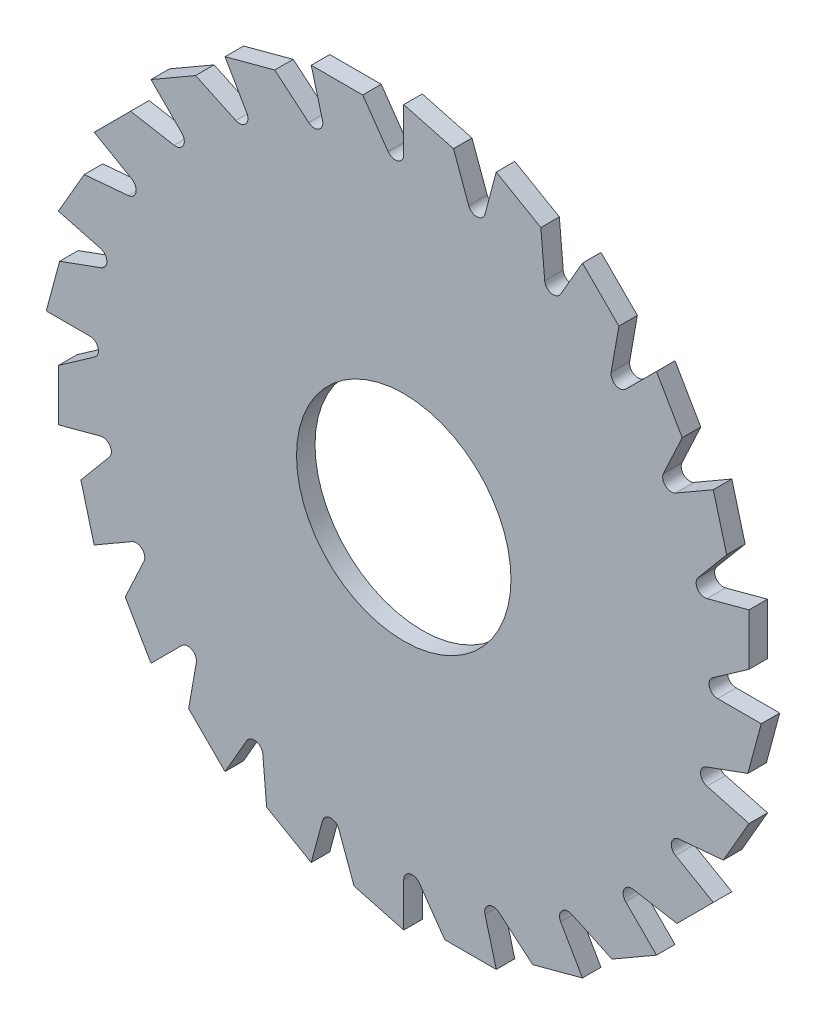
SolidWorks part; units mm, degrees
ref_plane "Front Plane" through (0, 0, 0) normal (0, 0, 1) x (1, 0, 0)
ref_plane "Top Plane" through (0, 0, 0) normal (0, 1, 0) x (1, 0, 0)
ref_plane "Right Plane" through (0, 0, 0) normal (1, 0, 0) x (0, 0, -1)
sketch "Sketch1" plane through (0, 0, 0) normal (0, 0, 1) x (1, 0, 0)
  line L0 (0, 31.75) -> (4.4162, 30.5667)
  line L1 (4.4162, 30.5667) -> (5.7634, 26.8652)
  line L2 (7.2155, 26.9286) -> (8.2175, 30.6681)
  line L3 (0, 31.75) -> (0, 0) construction
  line L4 (0, 0) -> (8.2175, 30.6681) construction
  line L5 (0, 31.75) -> (12.0811, 31.75) construction
  line L6 (6.3024, 26.3847) -> (0, 0) construction
  line L7 (6.3024, 26.3847) -> (4.0698, 26.918) construction
  line L8 (13.9393, 24.1436) -> (15.875, 27.4963)
  line L9 (12.177, 28.3821) -> (12.5203, 24.4581)
  line L10 (8.2175, 30.6681) -> (12.177, 28.3821)
  line L11 (19.7131, 19.7131) -> (22.4506, 22.4506)
  line L12 (19.1079, 24.2634) -> (18.4239, 20.3843)
  line L13 (15.875, 27.4963) -> (19.1079, 24.2634)
  line L14 (24.1436, 13.9393) -> (27.4963, 15.875)
  line L15 (24.7366, 18.4912) -> (23.072, 14.9212)
  line L16 (22.4506, 22.4506) -> (24.7366, 18.4912)
  line L17 (26.9286, 7.2155) -> (30.6681, 8.2175)
  line L18 (28.6796, 11.4588) -> (26.1477, 8.4413)
  line L19 (27.4963, 15.875) -> (28.6796, 11.4588)
  line L20 (27.8786, 0) -> (31.75, 0)
  line L21 (30.6681, 3.6455) -> (27.4415, 1.3862)
  line L22 (30.6681, 8.2175) -> (30.6681, 3.6455)
  line L23 (26.9286, -7.2155) -> (30.6681, -8.2175)
  line L24 (30.5667, -4.4162) -> (26.8652, -5.7634)
  line L25 (31.75, 0) -> (30.5667, -4.4162)
  line L26 (24.1436, -13.9393) -> (27.4963, -15.875)
  line L27 (28.3821, -12.177) -> (24.4581, -12.5203)
  line L28 (30.6681, -8.2175) -> (28.3821, -12.177)
  line L29 (19.7131, -19.7131) -> (22.4506, -22.4506)
  line L30 (24.2634, -19.1079) -> (20.3843, -18.4239)
  line L31 (27.4963, -15.875) -> (24.2634, -19.1079)
  line L32 (13.9393, -24.1436) -> (15.875, -27.4963)
  line L33 (18.4912, -24.7366) -> (14.9212, -23.072)
  line L34 (22.4506, -22.4506) -> (18.4912, -24.7366)
  line L35 (7.2155, -26.9286) -> (8.2175, -30.6681)
  line L36 (11.4588, -28.6796) -> (8.4413, -26.1477)
  line L37 (15.875, -27.4963) -> (11.4588, -28.6796)
  line L38 (0, -27.8786) -> (0, -31.75)
  line L39 (3.6455, -30.6681) -> (1.3862, -27.4415)
  line L40 (8.2175, -30.6681) -> (3.6455, -30.6681)
  line L41 (-7.2155, -26.9286) -> (-8.2175, -30.6681)
  line L42 (-4.4162, -30.5667) -> (-5.7634, -26.8652)
  line L43 (0, -31.75) -> (-4.4162, -30.5667)
  line L44 (-13.9393, -24.1436) -> (-15.875, -27.4963)
  line L45 (-12.177, -28.3821) -> (-12.5203, -24.4581)
  line L46 (-8.2175, -30.6681) -> (-12.177, -28.3821)
  line L47 (-19.7131, -19.7131) -> (-22.4506, -22.4506)
  line L48 (-19.1079, -24.2634) -> (-18.4239, -20.3843)
  line L49 (-15.875, -27.4963) -> (-19.1079, -24.2634)
  line L50 (-24.1436, -13.9393) -> (-27.4963, -15.875)
  line L51 (-24.7366, -18.4912) -> (-23.072, -14.9212)
  line L52 (-22.4506, -22.4506) -> (-24.7366, -18.4912)
  line L53 (-26.9286, -7.2155) -> (-30.6681, -8.2175)
  line L54 (-28.6796, -11.4588) -> (-26.1477, -8.4413)
  line L55 (-27.4963, -15.875) -> (-28.6796, -11.4588)
  line L56 (-27.8786, 0) -> (-31.75, 0)
  line L57 (-30.6681, -3.6455) -> (-27.4415, -1.3862)
  line L58 (-30.6681, -8.2175) -> (-30.6681, -3.6455)
  line L59 (-26.9286, 7.2155) -> (-30.6681, 8.2175)
  line L60 (-30.5667, 4.4162) -> (-26.8652, 5.7634)
  line L61 (-31.75, 0) -> (-30.5667, 4.4162)
  line L62 (-24.1436, 13.9393) -> (-27.4963, 15.875)
  line L63 (-28.3821, 12.177) -> (-24.4581, 12.5203)
  line L64 (-30.6681, 8.2175) -> (-28.3821, 12.177)
  line L65 (-19.7131, 19.7131) -> (-22.4506, 22.4506)
  line L66 (-24.2634, 19.1079) -> (-20.3843, 18.4239)
  line L67 (-27.4963, 15.875) -> (-24.2634, 19.1079)
  line L68 (-13.9393, 24.1436) -> (-15.875, 27.4963)
  line L69 (-18.4912, 24.7366) -> (-14.9212, 23.072)
  line L70 (-22.4506, 22.4506) -> (-18.4912, 24.7366)
  line L71 (-7.2155, 26.9286) -> (-8.2175, 30.6681)
  line L72 (-11.4588, 28.6796) -> (-8.4413, 26.1477)
  line L73 (-15.875, 27.4963) -> (-11.4588, 28.6796)
  line L74 (0, 27.8786) -> (0, 31.75)
  line L75 (-3.6455, 30.6681) -> (-1.3862, 27.4415)
  line L76 (-8.2175, 30.6681) -> (-3.6455, 30.6681)
  circle A0 centre (0, 0) radius 31.75 construction
  circle A1 centre (0, 0) radius 9.525
  circle A2 centre (0, 0) radius 27.127 construction
  arc A3 (5.7634, 26.8652) -> (7.2155, 26.9286) centre (6.4795, 27.1259) ccw
  arc A4 (12.5203, 24.4581) -> (13.9393, 24.1436) centre (13.2794, 24.5246) ccw
  arc A5 (18.4239, 20.3843) -> (19.7131, 19.7131) centre (19.1743, 20.2519) ccw
  arc A6 (23.072, 14.9212) -> (24.1436, 13.9393) centre (23.7626, 14.5992) ccw
  arc A7 (26.1477, 8.4413) -> (26.9286, 7.2155) centre (26.7314, 7.9515) ccw
  arc A8 (27.4415, 1.3862) -> (27.8786, 0) centre (27.8786, 0.762) ccw
  arc A9 (26.8652, -5.7634) -> (26.9286, -7.2155) centre (27.1259, -6.4795) ccw
  arc A10 (24.4581, -12.5203) -> (24.1436, -13.9393) centre (24.5246, -13.2794) ccw
  arc A11 (20.3843, -18.4239) -> (19.7131, -19.7131) centre (20.2519, -19.1743) ccw
  arc A12 (14.9212, -23.072) -> (13.9393, -24.1436) centre (14.5992, -23.7626) ccw
  arc A13 (8.4413, -26.1477) -> (7.2155, -26.9286) centre (7.9515, -26.7314) ccw
  arc A14 (1.3862, -27.4415) -> (0, -27.8786) centre (0.762, -27.8786) ccw
  arc A15 (-5.7634, -26.8652) -> (-7.2155, -26.9286) centre (-6.4795, -27.1259) ccw
  arc A16 (-12.5203, -24.4581) -> (-13.9393, -24.1436) centre (-13.2794, -24.5246) ccw
  arc A17 (-18.4239, -20.3843) -> (-19.7131, -19.7131) centre (-19.1743, -20.2519) ccw
  arc A18 (-23.072, -14.9212) -> (-24.1436, -13.9393) centre (-23.7626, -14.5992) ccw
  arc A19 (-26.1477, -8.4413) -> (-26.9286, -7.2155) centre (-26.7314, -7.9515) ccw
  arc A20 (-27.4415, -1.3862) -> (-27.8786, 0) centre (-27.8786, -0.762) ccw
  arc A21 (-26.8652, 5.7634) -> (-26.9286, 7.2155) centre (-27.1259, 6.4795) ccw
  arc A22 (-24.4581, 12.5203) -> (-24.1436, 13.9393) centre (-24.5246, 13.2794) ccw
  arc A23 (-20.3843, 18.4239) -> (-19.7131, 19.7131) centre (-20.2519, 19.1743) ccw
  arc A24 (-14.9212, 23.072) -> (-13.9393, 24.1436) centre (-14.5992, 23.7626) ccw
  arc A25 (-8.4413, 26.1477) -> (-7.2155, 26.9286) centre (-7.9515, 26.7314) ccw
  arc A26 (-1.3862, 27.4415) -> (0, 27.8786) centre (-0.762, 27.8786) ccw
  dimension "D1" = 63.5
  dimension "D2" = 19.05
  dimension "D3" = 125
  dimension "D7" = 0.762
  dimension "D4" = 15
  dimension "D5" = 15
  dimension "D6" = 4.572
  dimension "D8" = 24
extrude "Boss-Extrude1" add sketch "Sketch1" along normal blind 1.6444 contours A26 L75 L76 L71 A25 L72 L73 L68 A24 L69 L70 L65 A23 L66 L67 L62 A22 L63 L64 L59 A21 L60 L61 L56 A20 L57 L58 L53 A19 L54 L55 L50 A18 L51 L52 L47 A17 L48 L49 L44 A16 L45 L46 L41 A15 L42 L43 L38 A14 L39 L40 region at (1.9757, 30.2909, 0)
ref_plane "Plane1" through (0, 0, 0.8222) normal (0, 0, 1) x (1, 0, 0)
sketch "Sketch2" plane through (0, 0, 0) normal (0, 0, 1) x (1, 0, 0)
  line L0 (31.75, -31.75) -> (31.75, 31.75)
  line L1 (400.05, -31.75) -> (-31.75, -31.75)
  line L2 (400.05, -31.75) -> (400.05, 400.05)
  line L3 (400.05, 400.05) -> (-31.75, 400.05)
  line L4 (-31.75, -31.75) -> (-31.75, 400.05)
  line L5 (184.15, 400.05) -> (184.15, -31.75) construction
  line L6 (400.05, 184.15) -> (-31.75, 184.15) construction
  line L7 (-31.75, -31.75) -> (31.75, -31.75)
  line L8 (-31.75, -31.75) -> (-31.75, 31.75)
  line L9 (-31.75, 31.75) -> (31.75, 31.75)
  line L10 (31.75, -31.75) -> (31.75, 31.75)
  line L11 (0, 31.75) -> (0, -31.75) construction
  line L12 (-31.75, 0) -> (31.75, 0) construction
  line L13 (31.75, -31.75) -> (95.25, -31.75)
  line L14 (95.25, -31.75) -> (95.25, 31.75)
  line L15 (31.75, 31.75) -> (95.25, 31.75)
  line L16 (95.25, -31.75) -> (95.25, 31.75)
  line L17 (95.25, -31.75) -> (158.75, -31.75)
  line L18 (158.75, -31.75) -> (158.75, 31.75)
  line L19 (95.25, 31.75) -> (158.75, 31.75)
  line L20 (158.75, -31.75) -> (158.75, 31.75)
  line L21 (158.75, -31.75) -> (222.25, -31.75)
  line L22 (222.25, -31.75) -> (222.25, 31.75)
  line L23 (158.75, 31.75) -> (222.25, 31.75)
  line L24 (222.25, -31.75) -> (222.25, 31.75)
  line L25 (222.25, -31.75) -> (285.75, -31.75)
  line L26 (285.75, -31.75) -> (285.75, 31.75)
  line L27 (222.25, 31.75) -> (285.75, 31.75)
  line L28 (285.75, -31.75) -> (285.75, 31.75)
  line L29 (285.75, -31.75) -> (349.25, -31.75)
  line L30 (349.25, -31.75) -> (349.25, 31.75)
  line L31 (285.75, 31.75) -> (349.25, 31.75)
  line L32 (31.75, 31.75) -> (31.75, 95.25)
  line L33 (31.75, 31.75) -> (95.25, 31.75)
  line L34 (95.25, 31.75) -> (95.25, 95.25)
  line L35 (31.75, 95.25) -> (95.25, 95.25)
  line L36 (95.25, 31.75) -> (95.25, 95.25)
  line L37 (95.25, 31.75) -> (158.75, 31.75)
  line L38 (158.75, 31.75) -> (158.75, 95.25)
  line L39 (95.25, 95.25) -> (158.75, 95.25)
  line L40 (158.75, 31.75) -> (158.75, 95.25)
  line L41 (158.75, 31.75) -> (222.25, 31.75)
  line L42 (222.25, 31.75) -> (222.25, 95.25)
  line L43 (158.75, 95.25) -> (222.25, 95.25)
  line L44 (222.25, 31.75) -> (222.25, 95.25)
  line L45 (222.25, 31.75) -> (285.75, 31.75)
  line L46 (285.75, 31.75) -> (285.75, 95.25)
  line L47 (222.25, 95.25) -> (285.75, 95.25)
  line L48 (285.75, 31.75) -> (285.75, 95.25)
  line L49 (285.75, 31.75) -> (349.25, 31.75)
  line L50 (349.25, 31.75) -> (349.25, 95.25)
  line L51 (285.75, 95.25) -> (349.25, 95.25)
  line L52 (31.75, 95.25) -> (31.75, 158.75)
  line L53 (31.75, 95.25) -> (95.25, 95.25)
  line L54 (95.25, 95.25) -> (95.25, 158.75)
  line L55 (31.75, 158.75) -> (95.25, 158.75)
  line L56 (95.25, 95.25) -> (95.25, 158.75)
  line L57 (95.25, 95.25) -> (158.75, 95.25)
  line L58 (158.75, 95.25) -> (158.75, 158.75)
  line L59 (95.25, 158.75) -> (158.75, 158.75)
  line L60 (158.75, 95.25) -> (158.75, 158.75)
  line L61 (158.75, 95.25) -> (222.25, 95.25)
  line L62 (222.25, 95.25) -> (222.25, 158.75)
  line L63 (158.75, 158.75) -> (222.25, 158.75)
  line L64 (222.25, 95.25) -> (222.25, 158.75)
  line L65 (222.25, 95.25) -> (285.75, 95.25)
  line L66 (285.75, 95.25) -> (285.75, 158.75)
  line L67 (222.25, 158.75) -> (285.75, 158.75)
  line L68 (285.75, 95.25) -> (285.75, 158.75)
  line L69 (285.75, 95.25) -> (349.25, 95.25)
  line L70 (349.25, 95.25) -> (349.25, 158.75)
  line L71 (285.75, 158.75) -> (349.25, 158.75)
  line L72 (31.75, 158.75) -> (31.75, 222.25)
  line L73 (31.75, 158.75) -> (95.25, 158.75)
  line L74 (95.25, 158.75) -> (95.25, 222.25)
  line L75 (31.75, 222.25) -> (95.25, 222.25)
  line L76 (95.25, 158.75) -> (95.25, 222.25)
  line L77 (95.25, 158.75) -> (158.75, 158.75)
  line L78 (158.75, 158.75) -> (158.75, 222.25)
  line L79 (95.25, 222.25) -> (158.75, 222.25)
  line L80 (158.75, 158.75) -> (158.75, 222.25)
  line L81 (158.75, 158.75) -> (222.25, 158.75)
  line L82 (222.25, 158.75) -> (222.25, 222.25)
  line L83 (158.75, 222.25) -> (222.25, 222.25)
  line L84 (222.25, 158.75) -> (222.25, 222.25)
  line L85 (222.25, 158.75) -> (285.75, 158.75)
  line L86 (285.75, 158.75) -> (285.75, 222.25)
  line L87 (222.25, 222.25) -> (285.75, 222.25)
  line L88 (285.75, 158.75) -> (285.75, 222.25)
  line L89 (285.75, 158.75) -> (349.25, 158.75)
  line L90 (349.25, 158.75) -> (349.25, 222.25)
  line L91 (285.75, 222.25) -> (349.25, 222.25)
  line L92 (31.75, 222.25) -> (31.75, 285.75)
  line L93 (31.75, 222.25) -> (95.25, 222.25)
  line L94 (95.25, 222.25) -> (95.25, 285.75)
  line L95 (31.75, 285.75) -> (95.25, 285.75)
  line L96 (95.25, 222.25) -> (95.25, 285.75)
  line L97 (95.25, 222.25) -> (158.75, 222.25)
  line L98 (158.75, 222.25) -> (158.75, 285.75)
  line L99 (95.25, 285.75) -> (158.75, 285.75)
  line L100 (158.75, 222.25) -> (158.75, 285.75)
  line L101 (158.75, 222.25) -> (222.25, 222.25)
  line L102 (222.25, 222.25) -> (222.25, 285.75)
  line L103 (158.75, 285.75) -> (222.25, 285.75)
  line L104 (222.25, 222.25) -> (222.25, 285.75)
  line L105 (222.25, 222.25) -> (285.75, 222.25)
  line L106 (285.75, 222.25) -> (285.75, 285.75)
  line L107 (222.25, 285.75) -> (285.75, 285.75)
  line L108 (285.75, 222.25) -> (285.75, 285.75)
  line L109 (285.75, 222.25) -> (349.25, 222.25)
  line L110 (349.25, 222.25) -> (349.25, 285.75)
  line L111 (285.75, 285.75) -> (349.25, 285.75)
  line L112 (31.75, 285.75) -> (31.75, 349.25)
  line L113 (31.75, 285.75) -> (95.25, 285.75)
  line L114 (95.25, 285.75) -> (95.25, 349.25)
  line L115 (31.75, 349.25) -> (95.25, 349.25)
  line L116 (95.25, 285.75) -> (95.25, 349.25)
  line L117 (95.25, 285.75) -> (158.75, 285.75)
  line L118 (158.75, 285.75) -> (158.75, 349.25)
  line L119 (95.25, 349.25) -> (158.75, 349.25)
  line L120 (158.75, 285.75) -> (158.75, 349.25)
  line L121 (158.75, 285.75) -> (222.25, 285.75)
  line L122 (222.25, 285.75) -> (222.25, 349.25)
  line L123 (158.75, 349.25) -> (222.25, 349.25)
  line L124 (222.25, 285.75) -> (222.25, 349.25)
  line L125 (222.25, 285.75) -> (285.75, 285.75)
  line L126 (285.75, 285.75) -> (285.75, 349.25)
  line L127 (222.25, 349.25) -> (285.75, 349.25)
  line L128 (285.75, 285.75) -> (285.75, 349.25)
  line L129 (285.75, 285.75) -> (349.25, 285.75)
  line L130 (349.25, 285.75) -> (349.25, 349.25)
  line L131 (285.75, 349.25) -> (349.25, 349.25)
  line L132 (-31.75, 31.75) -> (-31.75, 95.25)
  line L133 (-31.75, 31.75) -> (31.75, 31.75)
  line L134 (31.75, 31.75) -> (31.75, 95.25)
  line L135 (-31.75, 95.25) -> (31.75, 95.25)
  line L136 (-31.75, 95.25) -> (-31.75, 158.75)
  line L137 (-31.75, 95.25) -> (31.75, 95.25)
  line L138 (31.75, 95.25) -> (31.75, 158.75)
  line L139 (-31.75, 158.75) -> (31.75, 158.75)
  line L140 (-31.75, 158.75) -> (-31.75, 222.25)
  line L141 (-31.75, 158.75) -> (31.75, 158.75)
  line L142 (31.75, 158.75) -> (31.75, 222.25)
  line L143 (-31.75, 222.25) -> (31.75, 222.25)
  line L144 (-31.75, 222.25) -> (-31.75, 285.75)
  line L145 (-31.75, 222.25) -> (31.75, 222.25)
  line L146 (31.75, 222.25) -> (31.75, 285.75)
  line L147 (-31.75, 285.75) -> (31.75, 285.75)
  line L148 (-31.75, 285.75) -> (-31.75, 349.25)
  line L149 (-31.75, 285.75) -> (31.75, 285.75)
  line L150 (31.75, 285.75) -> (31.75, 349.25)
  line L151 (-31.75, 349.25) -> (31.75, 349.25)
  line L152 (-31.75, -31.75) -> (31.75, -31.75) construction
  line L153 (-31.75, -31.75) -> (-31.75, 31.75) construction
  line L155 (-31.75, 400.05) -> (57.15, 400.05)
  line L156 (-31.75, 400.05) -> (-31.75, 349.25)
  line L157 (-31.75, 349.25) -> (57.15, 349.25)
  line L158 (57.15, 400.05) -> (57.15, 349.25)
  line L159 (57.15, 400.05) -> (146.05, 400.05)
  line L160 (57.15, 400.05) -> (57.15, 349.25)
  line L161 (57.15, 349.25) -> (146.05, 349.25)
  line L162 (146.05, 400.05) -> (146.05, 349.25)
  line L163 (146.05, 400.05) -> (234.95, 400.05)
  line L164 (146.05, 400.05) -> (146.05, 349.25)
  line L165 (146.05, 349.25) -> (234.95, 349.25)
  line L166 (234.95, 400.05) -> (234.95, 349.25)
  line L167 (234.95, 400.05) -> (323.85, 400.05)
  line L168 (234.95, 400.05) -> (234.95, 349.25)
  line L169 (234.95, 349.25) -> (323.85, 349.25)
  line L170 (323.85, 400.05) -> (323.85, 349.25)
  point P0 (184.15, 184.15)
  point P4 (0, 0)
  dimension "D1" = 431.8
  dimension "D2" = 431.8
  dimension "D3" = 63.5
  dimension "D4" = 6
  dimension "D6" = 63.5
  dimension "D7" = 63.5
  dimension "D8" = 88.9
  dimension "D9" = 88.9
  dimension "D10" = 88.9
  dimension "D11" = 88.9
  dimension "D5" = 6
equation "\"AVRG_T_Sprocket\"= ( 10 * 2 + 8 * 1.2 ) / 18mm"
equation "\"AVRG_T_NoSprocket\"= ( 9 * 2 + 8 * 1.2 ) / 18mm"
equation "\"D1@Boss-Extrude1\"=\"AVRG_T_Sprocket\""
